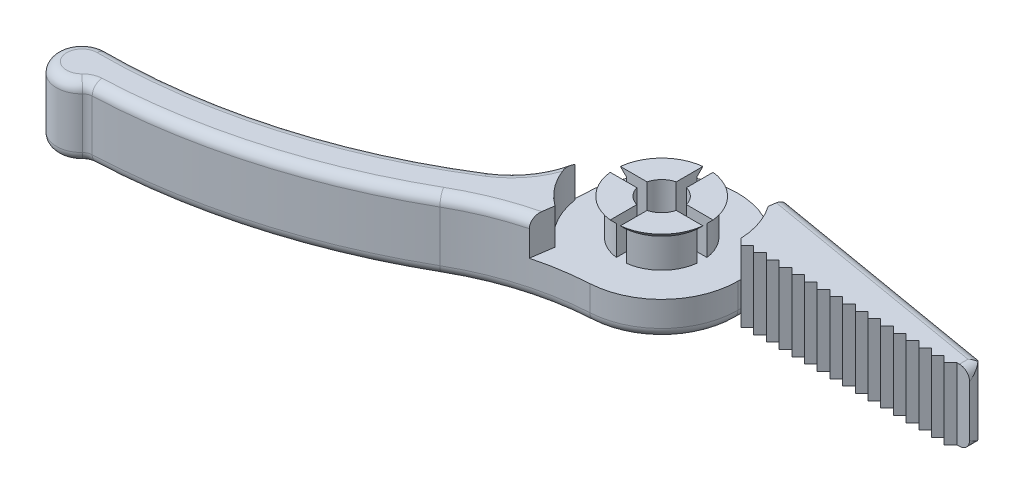
SolidWorks part; units mm, degrees
material "ABS"
ref_plane "Front Plane" through (0, 0, 0) normal (0, 0, 1) x (1, 0, 0)
ref_plane "Top Plane" through (0, 0, 0) normal (0, 1, 0) x (1, 0, 0)
ref_plane "Right Plane" through (0, 0, 0) normal (1, 0, 0) x (0, 0, -1)
sketch "Sketch1" plane through (0, 0, 0) normal (0, 1, 0) x (1, 0, 0)
  line L0 (-25.4, -74.0688) -> (-14.4062, -55.0269) construction
  line L1 (12.7, -73.6719) -> (12.7, -71.5288)
  line L2 (-19.8397, -65.9565) -> (12.7, -71.5288)
  line L3 (-76.2, -74.0688) -> (-76.2, -30.7147) construction
  line L4 (-25.4, -74.0688) -> (-76.2, -74.0688) construction
  line L5 (-15.875, -74.0688) -> (12.7, -74.0688) construction
  line L7 (-15.875, -74.0688) -> (-15.875, -73.6719)
  line L8 (11.1125, -73.6719) -> (10.3188, -74.4657)
  line L9 (10.3188, -74.4657) -> (9.525, -73.6719)
  line L10 (11.1125, -73.6719) -> (12.7, -73.6719)
  line L11 (9.525, -73.6719) -> (8.7313, -74.4657)
  line L12 (8.7313, -74.4657) -> (7.9375, -73.6719)
  line L13 (7.9375, -73.6719) -> (7.1438, -74.4657)
  line L14 (7.1438, -74.4657) -> (6.35, -73.6719)
  line L15 (6.35, -73.6719) -> (5.5563, -74.4657)
  line L16 (5.5563, -74.4657) -> (4.7625, -73.6719)
  line L17 (4.7625, -73.6719) -> (3.9688, -74.4657)
  line L18 (3.9688, -74.4657) -> (3.175, -73.6719)
  line L19 (3.175, -73.6719) -> (2.3813, -74.4657)
  line L20 (2.3813, -74.4657) -> (1.5875, -73.6719)
  line L21 (1.5875, -73.6719) -> (0.7938, -74.4657)
  line L22 (0.7938, -74.4657) -> (0, -73.6719)
  line L23 (0, -73.6719) -> (-0.7937, -74.4657)
  line L24 (-0.7937, -74.4657) -> (-1.5875, -73.6719)
  line L25 (-1.5875, -73.6719) -> (-2.3812, -74.4657)
  line L26 (-2.3812, -74.4657) -> (-3.175, -73.6719)
  line L27 (-3.175, -73.6719) -> (-3.9687, -74.4657)
  line L28 (-3.9687, -74.4657) -> (-4.7625, -73.6719)
  line L29 (-4.7625, -73.6719) -> (-5.5562, -74.4657)
  line L30 (-5.5562, -74.4657) -> (-6.35, -73.6719)
  line L31 (-6.35, -73.6719) -> (-7.1437, -74.4657)
  line L32 (-7.1437, -74.4657) -> (-7.9375, -73.6719)
  line L33 (-7.9375, -73.6719) -> (-8.7312, -74.4657)
  line L34 (-8.7312, -74.4657) -> (-9.525, -73.6719)
  line L35 (-9.525, -73.6719) -> (-10.3187, -74.4657)
  line L36 (-10.3187, -74.4657) -> (-11.1125, -73.6719)
  line L37 (-11.1125, -73.6719) -> (-11.9062, -74.4657)
  line L38 (-11.9062, -74.4657) -> (-12.7, -73.6719)
  line L39 (-12.7, -73.6719) -> (-13.4937, -74.4657)
  line L40 (-13.4937, -74.4657) -> (-14.2875, -73.6719)
  line L41 (-14.2875, -73.6719) -> (-15.0812, -74.4657)
  line L42 (-15.0812, -74.4657) -> (-15.875, -73.6719)
  circle A0 centre (-25.4, -74.0688) radius 5.08
  arc A1 (-33.9728, -69.9176) -> (-34.925, -74.0688) centre (-25.4, -74.0688) ccw
  arc A2 (-30.6107, -82.0422) -> (-15.875, -74.0688) centre (-25.4, -74.0688) ccw
  arc A3 (-21.2145, -65.5127) -> (-33.9728, -69.9176) centre (-25.4, -74.0688) ccw
  arc A4 (-39.2422, -81.8938) -> (-76.2, -92.5709) centre (-76.2, -23.2688) cw
  arc A5 (-30.6107, -82.0422) -> (-73.6272, -97.6064) centre (-76.2, -23.2688) cw
  arc A6 (-73.6272, -97.6064) -> (-76.2, -92.5709) centre (-76.2, -95.7459) cw
  arc A7 (-39.2422, -81.8938) -> (-34.925, -74.0688) centre (-44.1751, -74.0688) ccw
  arc A8 (-19.8397, -65.9565) -> (-21.2145, -65.5127) centre (-18.9822, -60.9494) cw
  point P17 (-20.6375, -65.8199)
  dimension "D1" = 10.16
  dimension "D2" = 19.05
  dimension "D6" = 5.08
  dimension "D3" = 38.1
  dimension "D4" = 2.54
  dimension "D5" = 1.5875
  dimension "D7" = 1.5875
extrude "Extrude1" add sketch "Sketch1" along normal blind 8.89
fillet "Fillet3" radius 33.02 1 edges at (-30.6107, 4.445, 82.0422)
sketch "Sketch4" plane through (0, 8.89, 0) normal (0, 1, 0) x (-1, 0, 0)
  line L0 (17.3035, 66.3908) -> (17.6206, 68.5727)
  line L2 (30.9835, 81.7857) -> (32.1538, 89.8378)
  line L3 (17.3035, 66.3908) -> (24.8129, 56.0079)
  line L4 (25.3271, 83.5935) -> (25.3271, 89.8378)
  line L5 (25.3271, 89.8378) -> (32.1538, 89.8378)
  line L6 (34.8297, 75.4131) -> (38.5061, 75.9372)
  line L7 (38.5061, 75.9372) -> (38.588, 69.7479)
  line L8 (24.8129, 56.0079) -> (38.588, 69.7479)
  line L9 (-12.7, 71.5288) -> (19.8397, 65.9565) construction
  arc A1 (25.3271, 83.5935) -> (17.6206, 68.5727) centre (25.4, 74.0688) ccw
  arc A2 (34.8297, 75.4131) -> (30.9835, 81.7857) centre (25.4, 74.0688) ccw
  point P5 (25.3271, 83.5935)
extrude "Cut-Extrude1" cut sketch "Sketch4" against normal blind 4.4704
fillet "Fillet4" radius 1.27 16 edges at (-73.6272, 4.445, 97.6064) (-3.5698, 0, 68.7427) (-20.5429, 0, 65.7837) (-30.4428, 0, 65.9882) (-36.4308, 8.89, 79.1274) (-36.0759, 0, 78.5373) (-56.9654, 8.89, 89.8481) (-56.9654, 0, 89.8481) (-79.0273, 8.89, 97.1904) (-79.0273, 0, 97.1904) (-35.4659, 8.89, 85.9854) (-15.875, 0, 73.8704) (-18.474, 0, 80.6076) (-32.337, 0, 84.8844) (-55.8837, 8.89, 94.8226) (-55.8837, 0, 94.8226)
fillet "Fillet7" radius 1.27 1 edges at (-2.3018, 8.89, 68.9598)
fillet "Fillet8" radius 2.54 3 edges at (12.7, 0.372, 71.9062) (12.7, 4.445, 71.5288) (12.7, 8.518, 71.9062)
sketch "Sketch7" plane through (0, 4.4196, 0) normal (0, 1, 0) x (-1, 0, 0)
  circle A0 centre (25.4, 74.0688) radius 9.5504
  dimension "D1" = 19.1008
extrude "Cut-Extrude5" cut sketch "Sketch7" along normal through all
sketch "Sketch8" plane through (0, 4.4196, 0) normal (0, 1, 0) x (-1, 0, 0)
  circle A0 centre (25.4, 74.0688) radius 5.08
extrude "Extrude2" add sketch "Sketch8" against normal up to surface (4.4196 mm away) up to face at (-9.7414, 0, 75.7444)
sketch "Sketch11" plane through (0, 4.4196, 0) normal (0, 1, 0) x (-1, 0, 0)
  line L0 (25.4, 69.0015) -> (25.4, 79.1361) construction
  line L1 (20.3327, 74.0688) -> (30.4673, 74.0688) construction
  line L2 (20.3726, 73.4338) -> (22.9407, 73.4338)
  line L3 (20.3726, 74.7038) -> (22.9407, 74.7038)
  line L4 (26.035, 69.0415) -> (26.035, 71.6095)
  line L5 (24.765, 69.0415) -> (24.765, 71.6095)
  line L6 (20.3327, 74.7038) -> (30.4673, 74.7038) construction
  line L7 (20.3327, 73.4338) -> (30.4673, 73.4338) construction
  line L8 (26.035, 69.0015) -> (26.035, 79.1361) construction
  line L9 (24.765, 69.0015) -> (24.765, 79.1361) construction
  line L10 (24.765, 76.5282) -> (24.765, 79.0962)
  line L11 (27.8593, 73.4338) -> (30.4274, 73.4338)
  line L12 (26.035, 76.5282) -> (26.035, 79.0962)
  line L13 (27.8593, 74.7038) -> (30.4274, 74.7038)
  arc A0 (30.4274, 74.7038) -> (26.035, 79.0962) centre (25.4, 74.0688) ccw
  arc A1 (26.035, 69.0415) -> (30.4274, 73.4338) centre (25.4, 74.0688) ccw
  arc A2 (20.3726, 73.4338) -> (24.765, 69.0415) centre (25.4, 74.0688) ccw
  arc A3 (24.765, 79.0962) -> (20.3726, 74.7038) centre (25.4, 74.0688) ccw
  arc A4 (24.765, 76.5282) -> (22.9407, 74.7038) centre (25.4, 74.0688) ccw
  arc A5 (27.8593, 74.7038) -> (26.035, 76.5282) centre (25.4, 74.0688) ccw
  arc A6 (26.035, 71.6095) -> (27.8593, 73.4338) centre (25.4, 74.0688) ccw
  arc A7 (22.9407, 73.4338) -> (24.765, 71.6095) centre (25.4, 74.0688) ccw
  dimension "D1" = 10.1346
  dimension "D6" = 5.08
  dimension "D2" = 0.635
  dimension "D3" = 0.635
  dimension "D4" = 0.635
  dimension "D5" = 0.635
extrude "Extrude3" add sketch "Sketch11" along normal blind 4.445 contours A0 L12 L13 | A1 L11 L4 | A2 L5 L2 | A3 L3 L10
sketch "Sketch12" plane through (0, 8.8646, 0) normal (0, 1, 0) x (-1, 0, 0)
  line L0 (24.765, 76.5282) -> (24.765, 79.8634)
  line L1 (22.9407, 74.7038) -> (19.6054, 74.7038)
  line L4 (20.3726, 74.7038) -> (22.9407, 74.7038)
  line L5 (24.765, 76.5282) -> (24.765, 79.0962)
  line L6 (20.3726, 74.7038) -> (22.9407, 74.7038)
  line L7 (24.765, 76.5282) -> (24.765, 79.0962)
  arc A0 (24.765, 76.5282) -> (22.9407, 74.7038) centre (25.4, 74.0688) ccw
  arc A1 (24.765, 79.8634) -> (19.6054, 74.7038) centre (25.4, 74.0688) ccw
  arc A3 (24.765, 76.5282) -> (22.9407, 74.7038) centre (25.4, 74.0688) ccw
  arc A4 (24.765, 79.0962) -> (20.3726, 74.7038) centre (25.4, 74.0688) ccw
  dimension "D1" = 0
extrude "Extrude4" add sketch "Sketch12" against normal blind 0.762 contours L0 A1 L1 A0
ref_axis "Axis1" through (-25.4, 8.8646, 74.0688) along (0, -1, 0)
pattern_circular "CirPattern1" count 4 over 360 about axis through (-25.4, 8.8646, 74.0688) along (0, -1, 0) of "Extrude4"
chamfer "Chamfer1" distance 0.762 angle 45 4 edges at (-29.5219, 8.1026, 69.9469) (-21.2781, 8.1026, 69.9469) (-29.5219, 8.1026, 78.1908) (-21.2781, 8.1026, 78.1908)
sketch "Sketch14" plane through (0, 4.4196, 0) normal (0, 1, 0) x (-1, 0, 0)
  circle A0 centre (25.4, 74.0688) radius 2.54
extrude "Cut-Extrude6" cut sketch "Sketch14" against normal through all
chamfer "Chamfer2" distance 1.27 angle 45 1 edges at (-25.4, 0, 76.6088)
sketch "Sketch15" plane through (0, 0, 73.4338) normal (0, 0, 1) x (1, 0, 0)
  line L1 (11.43, 8.89) -> (5.5562, 8.89)
  line L2 (12.7, 7.62) -> (12.7, 1.27)
  line L3 (11.43, 0) -> (5.5562, 0)
  arc A0 (12.7, 7.62) -> (11.43, 8.89) centre (11.43, 7.62) ccw
  arc A1 (11.43, 0) -> (12.7, 1.27) centre (11.43, 1.27) ccw
  point P8 (12.7, 8.89)
  dimension "D1" = 1.27
  dimension "D2" = 1.27
extrude "Cut-Extrude7" cut sketch "Sketch15" against normal through all and the other way through all flip side to cut
